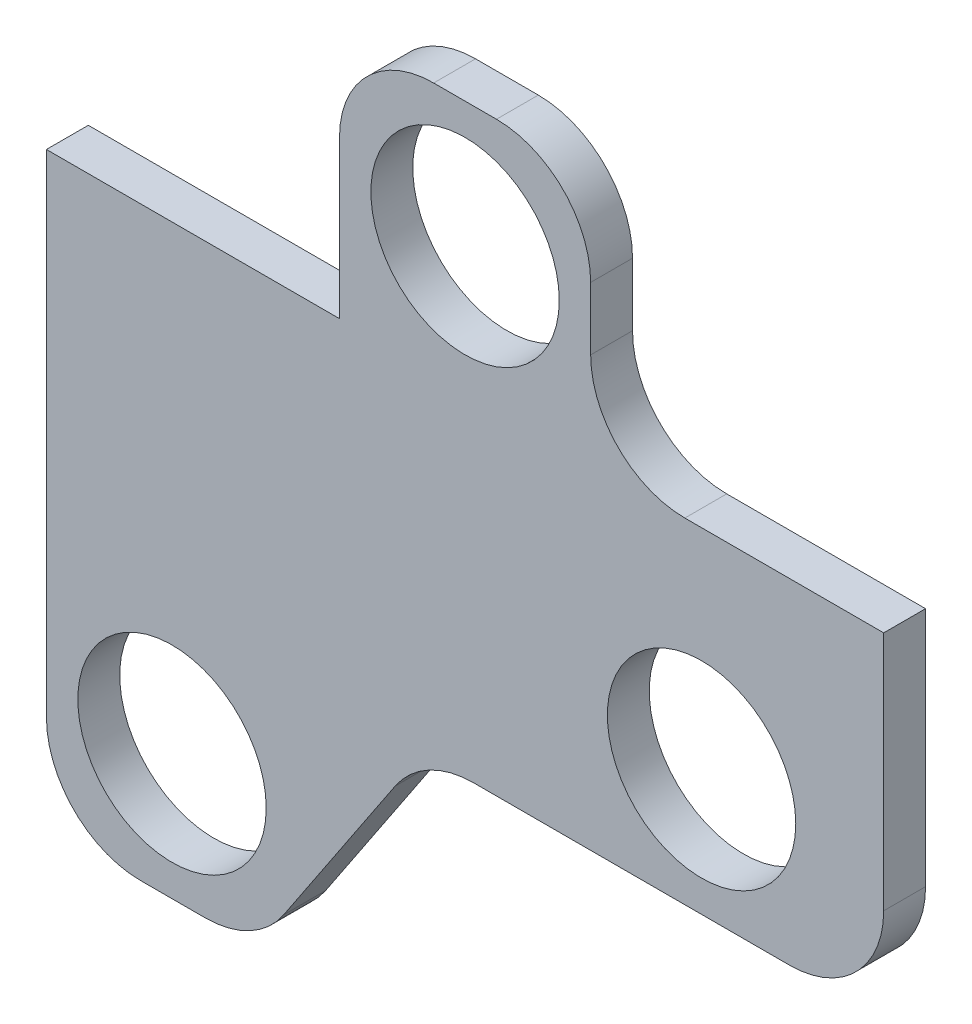
SolidWorks part; units mm, degrees
ref_plane "Front Plane" through (0, 0, 0) normal (0, 0, 1) x (1, 0, 0)
ref_plane "Top Plane" through (0, 0, 0) normal (0, 1, 0) x (1, 0, 0)
ref_plane "Right Plane" through (0, 0, 0) normal (1, 0, 0) x (0, 0, -1)
sketch "Sketch1" plane through (0, 0, 0) normal (0, 0, 1) x (1, 0, 0)
  line L0 (63.5, -6.35) -> (-6.35, -6.35)
  line L1 (-63.5, 44.45) -> (63.5, 44.45)
  line L2 (-63.5, 44.45) -> (-63.5, -44.45)
  line L3 (-63.5, -44.45) -> (63.5, -44.45)
  line L4 (63.5, 44.45) -> (63.5, -44.45)
  line L5 (-63.5, 44.45) -> (63.5, -44.45) construction
  line L6 (-63.5, -44.45) -> (63.5, 44.45) construction
  line L7 (-6.35, -6.35) -> (-31.75, -44.45)
  circle A0 centre (-44.45, -25.4) radius 14.2875
  circle A1 centre (35.8719, 12.7) radius 14.2875
  point P0 (0, 0)
  dimension "D1" = 28.575
  dimension "D2" = 28.575
  dimension "D3" = 88.9
  dimension "D4" = 19.05
  dimension "D5" = 57.15
  dimension "D6" = 88.9
  dimension "D7" = 19.05
  dimension "D8" = 127
  dimension "D9" = 38.1
  dimension "D10" = 31.75
  dimension "D11" = 57.15
extrude "Boss-Extrude1" add sketch "Sketch1" along normal blind 6.35 contours L7 L0 L4 L1 L2 L3 A1 A0 region at (-9.235, 13.2756, 0)
fillet "Fillet1" radius 14.2875 4 edges at (63.5, -6.35, 3.175) (-6.35, -6.35, 3.175) (-31.75, -44.45, 3.175) (-63.5, -44.45, 3.175)
sketch "Sketch2" plane through (0, 0, 6.35) normal (0, 0, 1) x (1, 0, 0)
  line L0 (-63.5, 44.45) -> (63.5, 44.45) construction
  line L1 (-19.05, 44.45) -> (19.05, 44.45)
  line L2 (-19.05, 44.45) -> (-19.05, 82.55)
  line L3 (-19.05, 82.55) -> (19.05, 82.55)
  line L4 (19.05, 44.45) -> (19.05, 82.55)
  line L5 (-63.5, 44.45) -> (-63.5, -30.1625) construction
  dimension "D1" = 38.1
  dimension "D2" = 44.45
  dimension "D3" = 38.1
extrude "Boss-Extrude2" add sketch "Sketch2" against normal blind 6.35
fillet "Fillet2" radius 14.2875 3 edges at (-19.05, 82.55, 3.175) (19.05, 82.55, 3.175) (19.05, 44.45, 3.175)
sketch "Sketch3" plane through (0, 0, 6.35) normal (0, 0, 1) x (1, 0, 0)
  line L0 (19.05, 58.7375) -> (19.05, 68.2625) construction
  line L1 (4.7625, 82.55) -> (-4.7625, 82.55) construction
  circle A0 centre (0, 63.5) radius 14.2875
  dimension "D1" = 28.575
  dimension "D2" = 19.05
  dimension "D3" = 19.05
extrude "Cut-Extrude1" cut sketch "Sketch3" against normal through all
